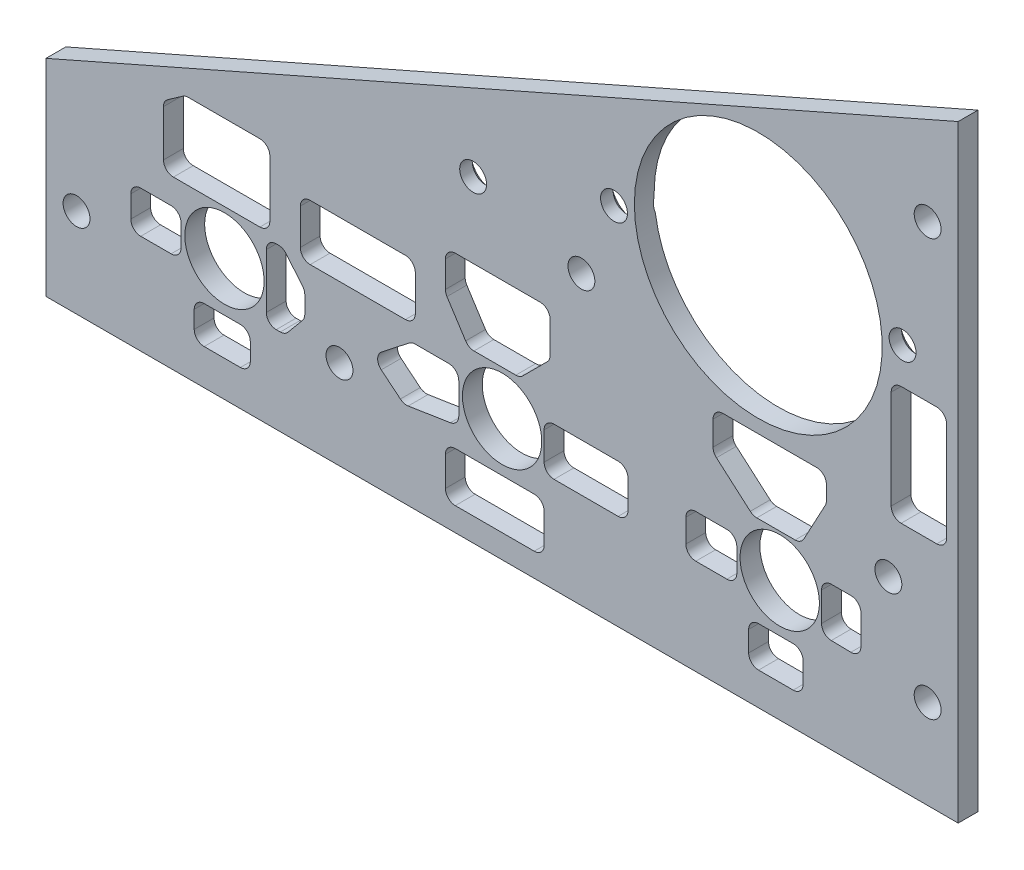
SolidWorks part; units mm, degrees
ref_plane "Front Plane" through (0, 0, 0) normal (0, 0, 1) x (1, 0, 0)
ref_plane "Top Plane" through (0, 0, 0) normal (0, 1, 0) x (1, 0, 0)
ref_plane "Right Plane" through (0, 0, 0) normal (1, 0, 0) x (0, 0, -1)
sketch "Sketch1" plane through (0, 0, 0) normal (0, 0, 1) x (1, 0, 0)
  line L4 (0, 97.282) -> (-146.05, 33.02)
  line L5 (-146.05, 33.02) -> (-146.05, 0)
  line L6 (-146.05, 0) -> (0, 0)
  line L7 (0, 0) -> (0, 97.282)
  line L8 (0, 97.282) -> (-146.05, 33.02)
  line L9 (-146.05, 33.02) -> (-146.05, 0)
  line L10 (-146.05, 0) -> (0, 0)
  line L11 (0, 0) -> (0, 97.282)
  dimension "D1" = 0
extrude "Boss-Extrude1" add sketch "Sketch1" against normal blind 3.175
hole_wizard "#6 Clearance Hole1" positions "Sketch6" profile "Sketch5" hole size "#6" standard "ANSI Inch" end condition through all
sketch "Sketch6" plane through (0, 0, -3.175) normal (0, 0, -1) x (-1, 0, 0)
  point P1 (4.8895, 80.9625)
  point P4 (4.8895, 14.2875)
  point P7 (141.1605, 14.2875)
  point P10 (11.176, 28.575)
  point P12 (60.325, 46.0375)
  point P14 (99.06, 14.2875)
sketch "Sketch5" plane through (-4.8895, 80.9625, -3.175) normal (1, 0, 0) x (0, 1, 0)
  line L0 (0, 0) -> (0, 3.175)
  line L1 (0, 3.175) -> (2.1526, 3.175)
  line L2 (2.1526, 3.175) -> (2.1526, 0)
  line L5 (2.1526, 0) -> (0, 0)
  line L11 (0, -6.35) -> (0, 107.95) construction
  dimension "Thru Hole Dia." = 4.3053
  dimension "Thru Hole Depth" = 3.175
sketch "Sketch7" plane through (0, 0, -3.175) normal (0, 0, -1) x (-1, 0, 0)
  circle A0 centre (32.004, 59.944) radius 19.8438 construction
  circle A1 centre (32.004, 59.944) radius 19.8438
  circle A2 centre (28.575, 19.3759) radius 6.35
  circle A3 centre (73.025, 19.558) radius 6.35
  circle A4 centre (117.475, 19.558) radius 6.35
  ellipse E0 centre (28.575, 21.3285) end of major axis (30.575, 21.3285) minor radius 1.9526 construction
  dimension "D1" = 12.7
extrude "Cut-Extrude1" cut sketch "Sketch7" against normal through all
hole_wizard "CSK for #6 Flat Head Machine Screw (100)1" positions "Sketch8" profile "Sketch9" countersink size "#6" standard "ANSI Inch" end condition up to next
sketch "Sketch8" plane through (0, 0, -3.175) normal (0, 0, -1) x (-1, 0, 0)
  point P0 (8.904, 61.8383)
  point P2 (55.104, 58.0497)
sketch "Sketch9" plane through (-8.904, 61.8383, -3.175) normal (1, 0, 0) x (0, 1, 0)
  line L0 (0, 0) -> (0, 3.175)
  line L1 (0, 3.175) -> (2.1526, 3.175)
  line L2 (2.1526, 3.175) -> (2.1526, 1.1669)
  line L3 (2.1526, 1.1669) -> (3.5433, 0)
  line L5 (3.5433, 0) -> (0, 0)
  line L6 (-2.1526, 1.1669) -> (-3.5433, 0) construction
  line L11 (0, -6.35) -> (0, 107.95) construction
  dimension "Thru Hole Dia." = 4.3053
  dimension "Thru Hole Depth" = 3.175
  dimension "Near C'Sink Dia." = 7.0866
  dimension "Near C'Sink Angle" = 100
sketch "Sketch15" plane through (0, 0, 0) normal (0, 0, -1) x (-1, 0, 0)
  line L0 (3.4308, 55.9821) -> (9.1402, 55.9821)
  line L1 (10.7277, 54.3946) -> (10.7277, 38.5968)
  line L2 (9.1402, 37.0093) -> (3.4308, 37.0093)
  line L3 (1.8433, 38.5968) -> (1.8433, 54.3946)
  line L4 (22.6774, 37.9781) -> (37.6629, 37.9781)
  line L5 (39.2504, 36.3906) -> (39.2504, 32.5074)
  line L6 (38.7044, 31.3093) -> (33.2838, 26.5969)
  line L7 (32.2423, 26.2075) -> (26.1089, 26.2075)
  line L8 (24.7106, 27.0433) -> (21.2791, 33.4267)
  line L9 (21.0899, 34.1784) -> (21.0899, 36.3906)
  line L10 (43.597, 20.6205) -> (43.597, 16.9025)
  line L11 (42.0095, 15.315) -> (37.0319, 15.315)
  line L12 (35.4444, 16.9025) -> (35.4444, 20.6205)
  line L13 (37.0319, 22.208) -> (42.0095, 22.208)
  line L14 (26.4141, 11.6802) -> (31.9586, 11.6802)
  line L15 (33.5461, 10.0927) -> (33.5461, 6.8245)
  line L16 (31.9586, 5.237) -> (26.4141, 5.237)
  line L17 (24.8266, 6.8245) -> (24.8266, 10.0927)
  line L18 (15.5717, 21.3809) -> (15.5717, 16.6831)
  line L19 (17.189, 15.0959) -> (20.3219, 15.1547)
  line L20 (21.8797, 16.7419) -> (21.8797, 21.3809)
  line L21 (20.2922, 22.9684) -> (17.1592, 22.9684)
  line L22 (54.4437, 22.9684) -> (64.7085, 22.9684)
  line L23 (66.296, 21.3809) -> (66.296, 16.9025)
  line L24 (64.7085, 15.315) -> (54.4437, 15.315)
  line L25 (52.8562, 16.9025) -> (52.8562, 21.3809)
  line L26 (67.8835, 11.6802) -> (80.5164, 11.6802)
  line L27 (82.1039, 10.0927) -> (82.1039, 5.3526)
  line L28 (80.5164, 3.7651) -> (67.8835, 3.7651)
  line L29 (66.296, 5.3526) -> (66.296, 10.0927)
  line L30 (79.9618, 21.3647) -> (79.9618, 16.4346)
  line L31 (81.3042, 14.8661) -> (88.0551, 13.8113)
  line L32 (89.3075, 14.1528) -> (92.372, 16.6689)
  line L33 (92.3433, 19.1457) -> (87.9131, 22.6146)
  line L34 (86.9344, 22.9522) -> (81.5493, 22.9522)
  line L35 (65.3361, 37.1822) -> (65.3361, 32.1953)
  line L36 (65.801, 31.0728) -> (69.703, 27.1708)
  line L37 (70.8256, 26.7058) -> (77.5253, 26.7058)
  line L38 (78.8606, 27.4347) -> (81.8516, 32.0861)
  line L39 (82.1039, 32.9447) -> (82.1039, 37.1822)
  line L40 (80.5164, 38.7697) -> (66.9236, 38.7697)
  line L41 (86.9196, 32.8897) -> (86.9196, 27.1599)
  line L42 (88.5071, 25.5724) -> (103.7481, 25.5724)
  line L43 (105.3356, 27.1599) -> (105.3356, 32.8897)
  line L44 (103.7481, 34.4772) -> (88.5071, 34.4772)
  line L45 (110.2115, 37.4103) -> (110.2115, 28.3414)
  line L46 (111.799, 26.7539) -> (125.6537, 26.7539)
  line L47 (127.2412, 28.3414) -> (127.2412, 35.7322)
  line L48 (126.5641, 37.0327) -> (124.167, 38.7108)
  line L49 (123.2566, 38.9978) -> (111.799, 38.9978)
  line L50 (126.0132, 15.9333) -> (130.8857, 15.9333)
  line L51 (132.4732, 17.5208) -> (132.4732, 21.0234)
  line L52 (130.8857, 22.6109) -> (126.0132, 22.6109)
  line L53 (124.4257, 21.0234) -> (124.4257, 17.5208)
  line L54 (114.9274, 11.6802) -> (120.7304, 11.6802)
  line L55 (122.3179, 10.0927) -> (122.3179, 7.3067)
  line L56 (120.7304, 5.7192) -> (114.9274, 5.7192)
  line L57 (113.3399, 7.3067) -> (113.3399, 10.0927)
  line L58 (110.7762, 15.4245) -> (110.7762, 24.1408)
  line L59 (109.1887, 25.7283) -> (108.8288, 25.7283)
  line L60 (107.6065, 25.1537) -> (104.9817, 21.986)
  line L61 (104.6165, 20.9731) -> (104.6165, 18.2321)
  line L62 (104.9816, 17.2192) -> (107.3081, 14.4116)
  line L63 (108.5304, 13.837) -> (109.1887, 13.837)
  line L64 (0, 0) -> (0, 97.282) construction
  line L65 (0, 0) -> (146.05, 0) construction
  arc A1 (104.6165, 18.2321) -> (104.9816, 17.2192) centre (106.204, 18.2321) ccw
  arc A2 (104.9817, 21.986) -> (104.6165, 20.9731) centre (106.204, 20.9731) ccw
  arc A3 (107.3081, 14.4116) -> (108.5304, 13.837) centre (108.5304, 15.4245) ccw
  arc A4 (110.7762, 24.1408) -> (109.1887, 25.7283) centre (109.1887, 24.1408) ccw
  arc A5 (108.8288, 25.7283) -> (107.6065, 25.1537) centre (108.8288, 24.1408) ccw
  arc A6 (110.7762, 15.4245) -> (109.1887, 13.837) centre (109.1887, 15.4245) cw
  arc A7 (126.0132, 22.6109) -> (124.4257, 21.0234) centre (126.0132, 21.0234) ccw
  arc A8 (132.4732, 21.0234) -> (130.8857, 22.6109) centre (130.8857, 21.0234) ccw
  arc A9 (130.8857, 15.9333) -> (132.4732, 17.5208) centre (130.8857, 17.5208) ccw
  arc A10 (126.0132, 15.9333) -> (124.4257, 17.5208) centre (126.0132, 17.5208) cw
  arc A11 (124.167, 38.7108) -> (123.2566, 38.9978) centre (123.2566, 37.4103) ccw
  arc A12 (125.6537, 26.7539) -> (127.2412, 28.3414) centre (125.6537, 28.3414) ccw
  arc A13 (127.2412, 35.7322) -> (126.5641, 37.0327) centre (125.6537, 35.7322) ccw
  arc A14 (110.2115, 28.3414) -> (111.799, 26.7539) centre (111.799, 28.3414) ccw
  arc A15 (105.3356, 32.8897) -> (103.7481, 34.4772) centre (103.7481, 32.8897) ccw
  arc A16 (110.2115, 37.4103) -> (111.799, 38.9978) centre (111.799, 37.4103) cw
  arc A17 (103.7481, 25.5724) -> (105.3356, 27.1599) centre (103.7481, 27.1599) ccw
  arc A18 (86.9196, 27.1599) -> (88.5071, 25.5724) centre (88.5071, 27.1599) ccw
  arc A19 (86.9196, 32.8897) -> (88.5071, 34.4772) centre (88.5071, 32.8897) cw
  arc A20 (82.1039, 37.1822) -> (80.5164, 38.7697) centre (80.5164, 37.1822) ccw
  arc A21 (77.5253, 26.7058) -> (78.8606, 27.4347) centre (77.5253, 28.2933) ccw
  arc A22 (81.8516, 32.0861) -> (82.1039, 32.9447) centre (80.5164, 32.9447) ccw
  arc A23 (69.703, 27.1708) -> (70.8256, 26.7058) centre (70.8256, 28.2933) ccw
  arc A24 (65.3361, 32.1953) -> (65.801, 31.0728) centre (66.9236, 32.1953) ccw
  arc A25 (87.9131, 22.6146) -> (86.9344, 22.9522) centre (86.9344, 21.3647) ccw
  arc A26 (65.3361, 37.1822) -> (66.9236, 38.7697) centre (66.9236, 37.1822) cw
  arc A27 (88.0551, 13.8113) -> (89.3075, 14.1528) centre (88.3002, 15.3797) ccw
  arc A28 (92.372, 16.6689) -> (92.3433, 19.1457) centre (91.3646, 17.8958) ccw
  arc A29 (79.9618, 16.4346) -> (81.3042, 14.8661) centre (81.5493, 16.4346) ccw
  arc A30 (79.9618, 21.3647) -> (81.5493, 22.9522) centre (81.5493, 21.3647) cw
  arc A31 (66.296, 16.9025) -> (64.7085, 15.315) centre (64.7085, 16.9025) cw
  arc A32 (54.4437, 15.315) -> (52.8562, 16.9025) centre (54.4437, 16.9025) cw
  arc A33 (64.7085, 22.9684) -> (66.296, 21.3809) centre (64.7085, 21.3809) cw
  arc A34 (21.8797, 21.3809) -> (20.2922, 22.9684) centre (20.2922, 21.3809) ccw
  arc A35 (54.4437, 22.9684) -> (52.8562, 21.3809) centre (54.4437, 21.3809) ccw
  arc A36 (20.3219, 15.1547) -> (21.8797, 16.7419) centre (20.2922, 16.7419) ccw
  arc A37 (15.5717, 16.6831) -> (17.189, 15.0959) centre (17.1592, 16.6831) ccw
  arc A38 (15.5717, 21.3809) -> (17.1592, 22.9684) centre (17.1592, 21.3809) cw
  arc A39 (33.5461, 6.8245) -> (31.9586, 5.237) centre (31.9586, 6.8245) cw
  arc A40 (26.4141, 5.237) -> (24.8266, 6.8245) centre (26.4141, 6.8245) cw
  arc A41 (31.9586, 11.6802) -> (33.5461, 10.0927) centre (31.9586, 10.0927) cw
  arc A42 (26.4141, 11.6802) -> (24.8266, 10.0927) centre (26.4141, 10.0927) ccw
  arc A43 (35.4444, 20.6205) -> (37.0319, 22.208) centre (37.0319, 20.6205) cw
  arc A44 (37.0319, 15.315) -> (35.4444, 16.9025) centre (37.0319, 16.9025) cw
  arc A45 (43.597, 16.9025) -> (42.0095, 15.315) centre (42.0095, 16.9025) cw
  arc A46 (43.597, 20.6205) -> (42.0095, 22.208) centre (42.0095, 20.6205) ccw
  arc A47 (21.2791, 33.4267) -> (21.0899, 34.1784) centre (22.6774, 34.1784) cw
  arc A48 (26.1089, 26.2075) -> (24.7106, 27.0433) centre (26.1089, 27.795) cw
  arc A49 (39.2504, 32.5074) -> (38.7044, 31.3093) centre (37.6629, 32.5074) cw
  arc A50 (33.2838, 26.5969) -> (32.2423, 26.2075) centre (32.2423, 27.795) cw
  arc A51 (37.6629, 37.9781) -> (39.2504, 36.3906) centre (37.6629, 36.3906) cw
  arc A52 (3.4308, 37.0093) -> (1.8433, 38.5968) centre (3.4308, 38.5968) cw
  arc A53 (22.6774, 37.9781) -> (21.0899, 36.3906) centre (22.6774, 36.3906) ccw
  arc A54 (10.7277, 38.5968) -> (9.1402, 37.0093) centre (9.1402, 38.5968) cw
  arc A55 (9.1402, 55.9821) -> (10.7277, 54.3946) centre (9.1402, 54.3946) cw
  arc A56 (3.4308, 55.9821) -> (1.8433, 54.3946) centre (3.4308, 54.3946) ccw
  arc A57 (114.9274, 5.7192) -> (113.3399, 7.3067) centre (114.9274, 7.3067) cw
  arc A58 (122.3179, 7.3067) -> (120.7304, 5.7192) centre (120.7304, 7.3067) cw
  arc A59 (120.7304, 11.6802) -> (122.3179, 10.0927) centre (120.7304, 10.0927) cw
  arc A60 (114.9274, 11.6802) -> (113.3399, 10.0927) centre (114.9274, 10.0927) ccw
  arc A61 (82.1039, 5.3526) -> (80.5164, 3.7651) centre (80.5164, 5.3526) cw
  arc A62 (67.8835, 3.7651) -> (66.296, 5.3526) centre (67.8835, 5.3526) cw
  arc A63 (80.5164, 11.6802) -> (82.1039, 10.0927) centre (80.5164, 10.0927) cw
  arc A64 (67.8835, 11.6802) -> (66.296, 10.0927) centre (67.8835, 10.0927) ccw
  point P134 (21.8797, 22.9684)
  point P139 (21.8797, 15.1839)
  point P150 (33.5461, 11.6802)
  point P159 (43.597, 15.315)
  point P196 (82.1039, 11.6802)
  dimension "D1" = 1.5875
extrude "Cut-Extrude4" cut sketch "Sketch15" along normal through all
hole_wizard "CSK for #6 Flat Head Machine Screw (100)2" positions "Sketch16" profile "Sketch17" countersink size "#6" standard "ANSI Inch" end condition through all
sketch "Sketch16" plane through (0, 0, -3.175) normal (0, 0, -1) x (-1, 0, 0)
  line L0 (146.05, 0) -> (0, 0) construction
  circle A0 centre (141.1605, 14.2875) radius 2.1527 construction
  point P0 (77.6605, 50.8)
  point P2 (77.6605, 50.8)
  point P5 (75.2857, 53.8291)
  dimension "D1" = 63.5
  dimension "D2" = 50.8
sketch "Sketch17" plane through (-77.6605, 50.8, -3.175) normal (1, 0, 0) x (0, 1, 0)
  line L0 (0, 0) -> (0, 3.175)
  line L1 (0, 3.175) -> (2.1526, 3.175)
  line L2 (2.1526, 3.175) -> (2.1526, 1.1669)
  line L3 (2.1526, 1.1669) -> (3.5433, 0)
  line L5 (3.5433, 0) -> (0, 0)
  line L6 (-2.1526, 1.1669) -> (-3.5433, 0) construction
  line L11 (0, -6.35) -> (0, 107.95) construction
  dimension "Thru Hole Dia." = 4.3053
  dimension "Thru Hole Depth" = 3.175
  dimension "Near C'Sink Dia." = 7.0866
  dimension "Near C'Sink Angle" = 100
